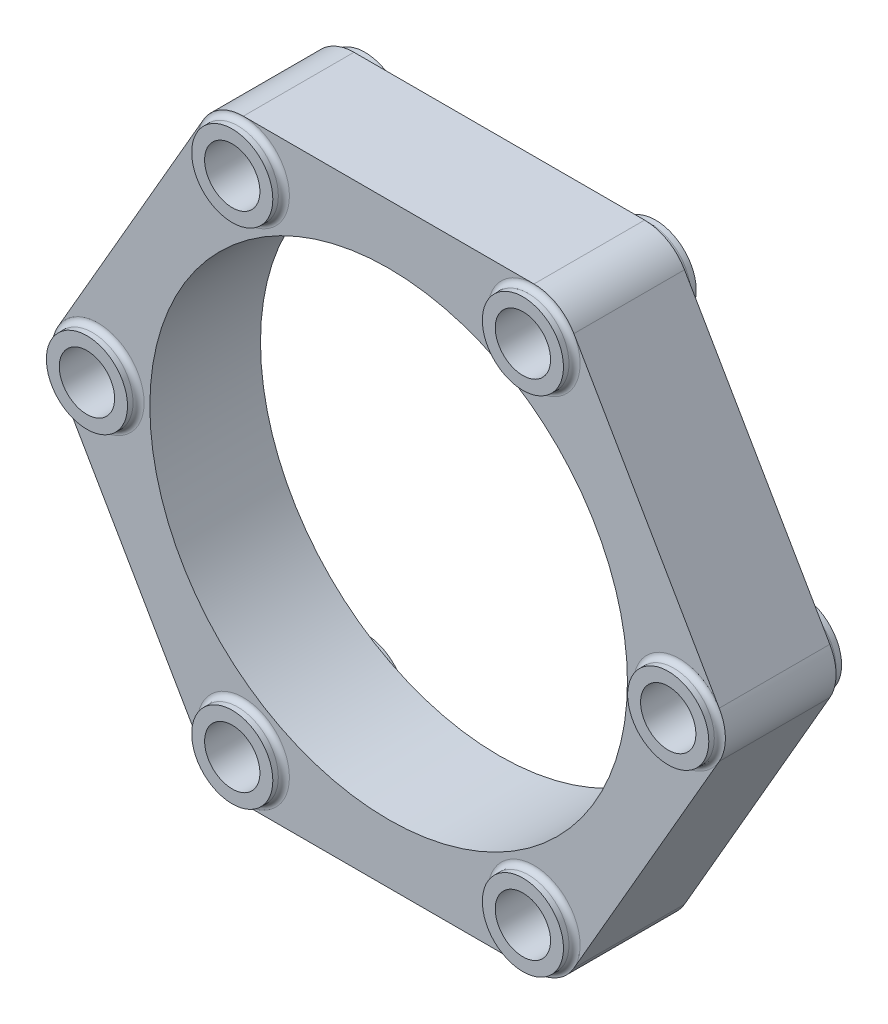
SolidWorks part; units mm, degrees
material "PPE"
ref_plane "Front Plane" through (0, 0, 0) normal (0, 0, 1) x (1, 0, 0)
ref_plane "Top Plane" through (0, 0, 0) normal (0, 1, 0) x (1, 0, 0)
ref_plane "Right Plane" through (0, 0, 0) normal (1, 0, 0) x (0, 0, -1)
sketch "Sketch1" plane through (0, 0, 0) normal (0, 0, 1) x (1, 0, 0)
  line L0 (-89.6353, 6.25) -> (-50.2303, 74.5015)
  line L1 (-39.405, 80.7515) -> (39.405, 80.7515)
  line L2 (50.2303, 74.5015) -> (89.6353, 6.25)
  line L3 (89.6353, -6.25) -> (50.2303, -74.5015)
  line L4 (39.405, -80.7515) -> (-39.405, -80.7515)
  line L5 (-50.2303, -74.5015) -> (-89.6353, -6.25)
  circle A0 centre (0, 0) radius 78.81 construction
  arc A1 (-89.6353, 6.25) -> (-89.6353, -6.25) centre (-78.81, 0) ccw
  arc A2 (-39.405, 80.7515) -> (-50.2303, 74.5015) centre (-39.405, 68.2515) ccw
  arc A3 (50.2303, 74.5015) -> (39.405, 80.7515) centre (39.405, 68.2515) ccw
  arc A4 (89.6353, -6.25) -> (89.6353, 6.25) centre (78.81, 0) ccw
  arc A5 (39.405, -80.7515) -> (50.2303, -74.5015) centre (39.405, -68.2515) ccw
  arc A6 (-50.2303, -74.5015) -> (-39.405, -80.7515) centre (-39.405, -68.2515) ccw
  circle A8 centre (0, 0) radius 64.75
  point P17 (0, 0)
  point P30 (0, 0)
  dimension "D1" = 157.62
  dimension "D2" = 25
  dimension "D5" = 129.5
  dimension "D3" = 6
  dimension "D4" = 6
extrude "Boss-Extrude1" add sketch "Sketch1" along normal mid plane 30
sketch "Sketch2" plane through (0, 0, 0) normal (0, 0, 1) x (1, 0, 0)
  circle A0 centre (-78.81, 0) radius 11
  circle A1 centre (-39.405, 68.2515) radius 11
  circle A2 centre (39.405, 68.2515) radius 11
  circle A3 centre (78.81, 0) radius 11
  circle A4 centre (39.405, -68.2515) radius 11
  circle A5 centre (-39.405, -68.2515) radius 11
  point P16 (0, 0)
  dimension "D1" = 22
  dimension "D2" = 6
extrude "Boss-Extrude2" add sketch "Sketch2" along normal mid plane 36
sketch "Sketch4" plane through (0, 0, 18) normal (0, 0, 1) x (1, 0, 0)
  circle A0 centre (-78.81, 0) radius 7.5
  circle A1 centre (-39.405, 68.2515) radius 7.5
  circle A2 centre (39.405, 68.2515) radius 7.5
  circle A3 centre (78.81, 0) radius 7.5
  circle A4 centre (39.405, -68.2515) radius 7.5
  circle A5 centre (-39.405, -68.2515) radius 7.5
  point P15 (0, 0)
  dimension "D1" = 15
  dimension "D2" = 6
extrude "Cut-Extrude1" cut sketch "Sketch4" against normal up to next
fillet "Fillet1" radius 1.5 12 edges at (50.405, 68.2515, -15) (89.81, 0, -15) (-28.405, 68.2515, -15) (-67.81, 0, -15) (50.405, -68.2515, -15) (-28.405, -68.2515, -15) (89.81, 0, 15) (50.405, -68.2515, 15) (-67.81, 0, 15) (-28.405, -68.2515, 15) (50.405, 68.2515, 15) (-28.405, 68.2515, 15)
